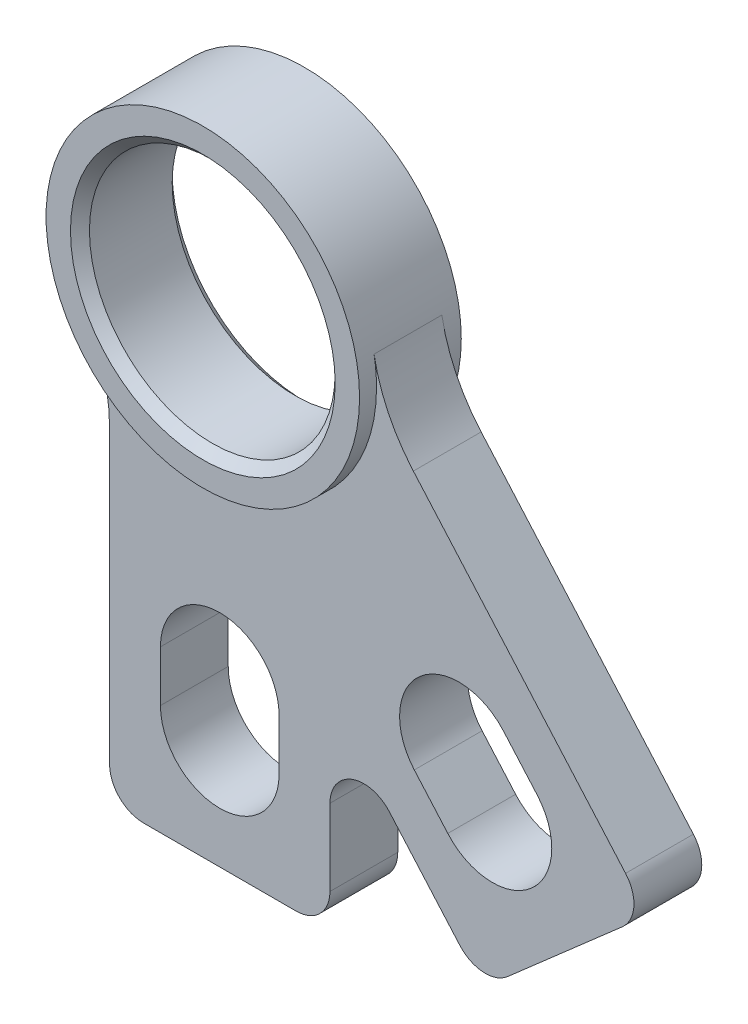
SolidWorks part; units mm, degrees
material "AISI 4130 Steel, annealed at 865C"
ref_plane "X-Y Datum" through (0, 0, 0) normal (0, 0, 1) x (1, 0, 0)
ref_plane "X-Z Datum" through (0, 0, 0) normal (0, 1, 0) x (1, 0, 0)
ref_plane "Y-Z Datum" through (0, 0, 0) normal (1, 0, 0) x (0, 0, -1)
sketch "Sketch1" plane through (0, 0, 0) normal (0, 0, 1) x (1, 0, 0)
  line L0 (0, -35.8956) -> (0, -31.1331) construction
  line L1 (-5.5562, -35.8956) -> (-5.5562, -31.1331)
  line L2 (5.5562, -35.8956) -> (5.5562, -31.1331)
  line L3 (25.5355, -29.1502) -> (22.3974, -25.5679) construction
  line L4 (21.3561, -32.8114) -> (18.218, -29.229)
  line L5 (29.715, -25.4891) -> (26.5768, -21.9067)
  line L6 (-10.3187, -15.7343) -> (-10.3187, -46.2143)
  line L7 (-10.3187, -46.2143) -> (10.3187, -46.2143)
  line L10 (24.5731, -43.7114) -> (40.0967, -30.1127)
  line L11 (40.0967, -30.1127) -> (18.1296, -5.0361)
  line L12 (10.3187, -46.2143) -> (10.3187, -27.4393)
  line L13 (224.1242, -255.8501) -> (0, 0) construction
  line L14 (0, -41.4518) -> (0, -46.2143) construction
  line L15 (29.1967, -33.3297) -> (32.3349, -36.912) construction
  line L16 (28.1459, -23.6979) -> (31.7283, -20.5597) construction
  line L17 (-5.5562, -33.5143) -> (-10.3187, -33.5143) construction
  line L18 (-10.3187, -20.8143) -> (10.3187, -20.8143) construction
  line L19 (10.3187, -20.8143) -> (10.3187, -46.2143) construction
  line L20 (5.5562, -33.5143) -> (10.3187, -33.5143) construction
  line L21 (0, -25.5768) -> (0, -20.8143) construction
  line L22 (24.5731, -43.7114) -> (7.8363, -24.6054) construction
  line L23 (7.8363, -24.6054) -> (23.3599, -11.0067) construction
  line L24 (19.787, -31.0202) -> (16.2047, -34.1584) construction
  line L25 (18.7362, -21.3884) -> (15.5981, -17.8061) construction
  line L29 (24.5731, -43.7114) -> (10.3187, -27.4393)
  line L30 (0, -348.1463) -> (0, 0) construction
  line L31 (0, -347.9572) -> (0, 0) construction
  line L32 (207.5784, -236.9622) -> (-0.0442, 0.0505) construction
  circle A0 centre (0, 0) radius 11.5062
  arc A1 (-5.5562, -35.8956) -> (5.5562, -35.8956) centre (0, -35.8956) ccw
  arc A2 (5.5562, -31.1331) -> (-5.5562, -31.1331) centre (0, -31.1331) ccw
  arc A3 (21.3561, -32.8114) -> (29.715, -25.4891) centre (25.5355, -29.1502) ccw
  arc A4 (26.5768, -21.9067) -> (18.218, -29.229) centre (22.3974, -25.5679) ccw
  arc A5 (14.448, 2.6062) -> (-12.5852, -7.5598) centre (0, 0) ccw
  arc A6 (18.1296, -5.0361) -> (14.448, 2.6062) centre (30.0709, 5.4244) cw
  arc A7 (-10.3187, -15.7343) -> (-12.5852, -7.5598) centre (-26.1937, -15.7343) ccw
  arc A14 (-12.5852, -7.5598) -> (14.448, 2.6062) centre (0, 0) ccw
  point P5 (0, -33.5143)
  point P11 (23.9665, -27.359)
  point P24 (32.3349, -36.912)
  point P39 (29.1967, -33.3297)
  dimension "D1" = 23.0124
  dimension "D2" = 3.175
  dimension "D8" = 15.875
  dimension "D6" = 7.9375
  dimension "D7" = 5.08
  dimension "D3" = 20.6375
  dimension "D4" = 4.7625
  dimension "D5" = 25.4
extrude "Boss-Extrude2" add sketch "Sketch1" along normal mid plane 9.525 contours A5 A14 A0 region at (-5.0215, 13.353, 0)
extrude "Boss-Extrude3" add sketch "Sketch1<4>" along normal mid plane 6.35 contours L29 L10 L11 A6 A14 A7 L6 L7 A4 L5 A3 L4 A2 L2 A1 L1 region at (10.618, -25.9346, 0)
sketch "Sketch1<4>" plane through (0, 0, 0) normal (0, 0, 1) x (1, 0, 0) same geometry as "Sketch1"
fillet "Fillet1" radius 3.175 5 edges at (-10.3187, -46.2143, 0) (40.0967, -30.1127, 0) (10.3187, -27.4393, 0) (24.5731, -43.7114, 0) (10.3187, -46.2143, 0)
chamfer "Chamfer1" distance 0.889 angle 45 2 edges at (11.5062, 0, -4.7625) (11.5062, 0, 4.7625)
fillet "Fillet2" [suppressed] radius 1.27
